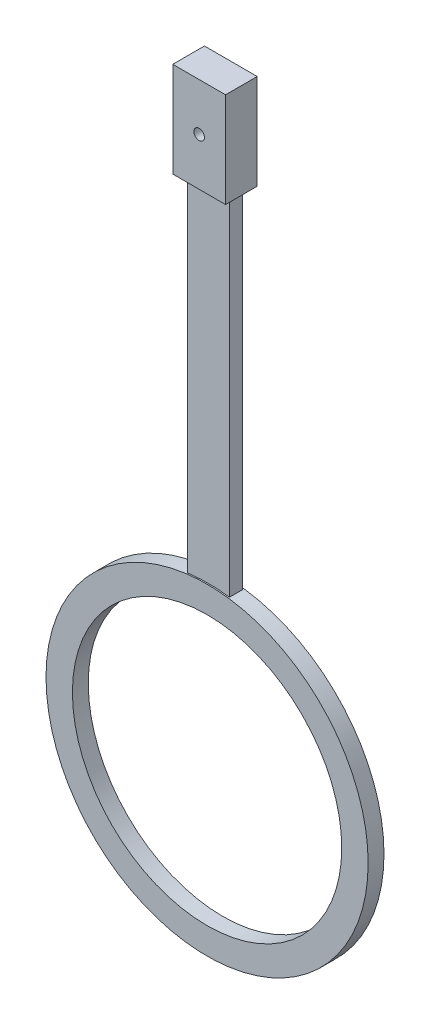
SolidWorks part; units mm, degrees
ref_plane "Front Plane" through (0, 0, 0) normal (0, 0, 1) x (1, 0, 0)
ref_plane "Top Plane" through (0, 0, 0) normal (0, 1, 0) x (1, 0, 0)
ref_plane "Right Plane" through (0, 0, 0) normal (1, 0, 0) x (0, 0, -1)
sketch "Sketch1" plane through (0, 0, 0) normal (0, 0, 1) x (1, 0, 0)
  circle A0 centre (0, 0) radius 30.5
  dimension "D1" = 61
extrude "Boss-Extrude1" add sketch "Sketch1" along normal mid plane 3
sketch "Sketch2" plane through (0, 0, 0) normal (0, 0, 1) x (1, 0, 0)
  line L0 (-4, 25) -> (4, 25)
  line L1 (4, 25) -> (4, 96)
  line L2 (4, 96) -> (-4, 96)
  line L3 (-4, 96) -> (-4, 25)
extrude "Boss-Extrude2" add sketch "Sketch2" along normal mid plane 2.5
sketch "Sketch3" plane through (0, 0, 0) normal (0, 0, 1) x (1, 0, 0)
  line L0 (-5, 96) -> (5, 96)
  line L1 (5, 96) -> (5, 114)
  line L2 (5, 114) -> (-5, 114)
  line L3 (-5, 114) -> (-5, 96)
extrude "Boss-Extrude3" add sketch "Sketch3" along normal mid plane 6
sketch "Sketch4" plane through (0, 0, 0) normal (0, 0, 1) x (1, 0, 0)
  circle A0 centre (0, 0) radius 25.5
  dimension "D1" = 51
extrude "Cut-Extrude1" cut sketch "Sketch4" against normal mid plane 20
sketch "Sketch5" plane through (0, 0, 0) normal (0, 0, 1) x (1, 0, 0)
  circle A0 centre (0, 105) radius 1
  dimension "D1" = 2
extrude "Cut-Extrude2" cut sketch "Sketch5" against normal mid plane 20
